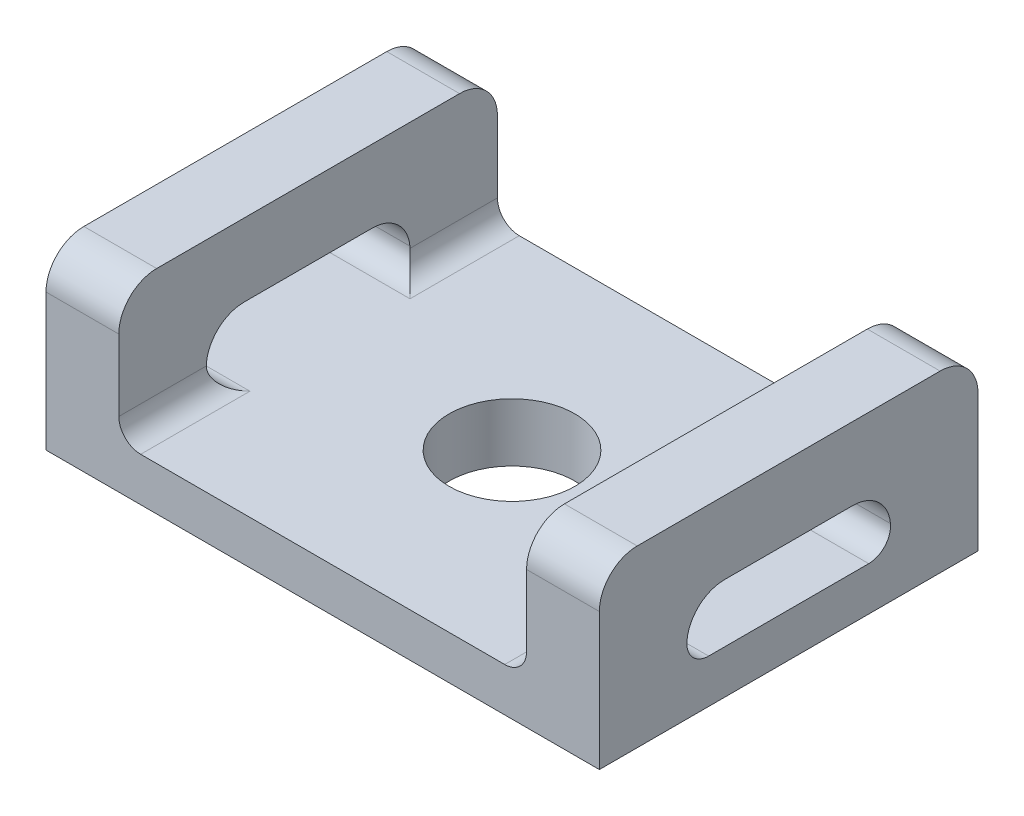
SolidWorks part; units mm, degrees
ref_plane "Front Plane" through (0, 0, 0) normal (0, 0, 1) x (1, 0, 0)
ref_plane "Top Plane" through (0, 0, 0) normal (0, 1, 0) x (1, 0, 0)
ref_plane "Right Plane" through (0, 0, 0) normal (1, 0, 0) x (0, 0, -1)
sketch "Sketch1" plane through (0, 0, 0) normal (0, 1, 0) x (1, 0, 0)
  line L1 (-9.5, -6.5) -> (9.5, -6.5)
  line L2 (-9.5, -6.5) -> (-9.5, 6.5)
  line L3 (-9.5, 6.5) -> (9.5, 6.5)
  line L4 (9.5, -6.5) -> (9.5, 6.5)
  line L5 (-9.5, -6.5) -> (9.5, 6.5) construction
  line L6 (-9.5, 6.5) -> (9.5, -6.5) construction
  circle A0 centre (0, 0) radius 2.159
  point P0 (0, 0)
  dimension "D3" = 4.318
  dimension "D1" = 19
  dimension "D2" = 13
extrude "Boss-Extrude1" add sketch "Sketch1" along normal blind 2
sketch "Sketch2" plane through (9.5, 0, 0) normal (1, 0, 0) x (0, 0, -1)
  line L1 (-6.5, 2) -> (6.5, 2)
  line L2 (-6.5, 2) -> (-6.5, 5.2)
  line L3 (-5.2, 6.5) -> (5.2, 6.5)
  line L4 (6.5, 2) -> (6.5, 5.2)
  line L5 (-3.5, 2) -> (3.5, 2)
  line L6 (-3.5, 2) -> (-3.5, 2.7)
  line L7 (-2.2, 4) -> (2.2, 4)
  line L8 (3.5, 2) -> (3.5, 2.7)
  arc A0 (3.5, 2.7) -> (2.2, 4) centre (2.2, 2.7) ccw
  arc A1 (-2.2, 4) -> (-3.5, 2.7) centre (-2.2, 2.7) ccw
  arc A2 (5.2, 6.5) -> (6.5, 5.2) centre (5.2, 5.2) cw
  arc A3 (-6.5, 5.2) -> (-5.2, 6.5) centre (-5.2, 5.2) cw
  point P13 (-3.5, 4)
  point P16 (6.5, 6.5)
  point P19 (-6.5, 6.5)
  line M8 (6.5, 2) -> (-6.5, 2)
  dimension "D6" = 1.3
  dimension "D7" = 1.3
  dimension "D1" = 13
  dimension "D2" = 4.5
  dimension "D3" = 3
  dimension "D4" = 3
  dimension "D5" = 2
extrude "Boss-Extrude2" add sketch "Sketch2" against normal blind 19 contours A3 L2 L6 A1 L7 A0 L8 L4 A2 L3 M8 region at (9.5, 4.6025, 0)
sketch "Sketch4" plane through (0, 0, 6.5) normal (0, 0, 1) x (1, 0, 0)
  line L0 (-9.5, 5.2) -> (-9.5, 0) construction
  line L1 (-7, 7) -> (7, 7)
  line L2 (-7, 7) -> (-7, 2)
  line L3 (-7, 2) -> (7, 2)
  line L4 (7, 7) -> (7, 2)
  line L5 (-9.5, 0) -> (9.5, 0) construction
  dimension "D1" = 2.5
  dimension "D2" = 2.5
  dimension "D3" = 2
  dimension "D4" = 5
extrude "Cut-Extrude1" cut sketch "Sketch4" against normal through all both and the other way through all
fillet "Fillet1" radius 0.75 8 edges at (-7, 2, 5) (-8.25, 2, 3.5) (8.25, 2, 3.5) (7, 2, 5) (7, 2, -5) (8.25, 2, -3.5) (-7, 2, -5) (-8.25, 2, -3.5)
chamfer "Chamfer1" distance 0.5 angle 45 4 edges at (0, 0, -6.5) (-9.5, 0, 0) (0, 0, 6.5) (9.5, 0, 0)
